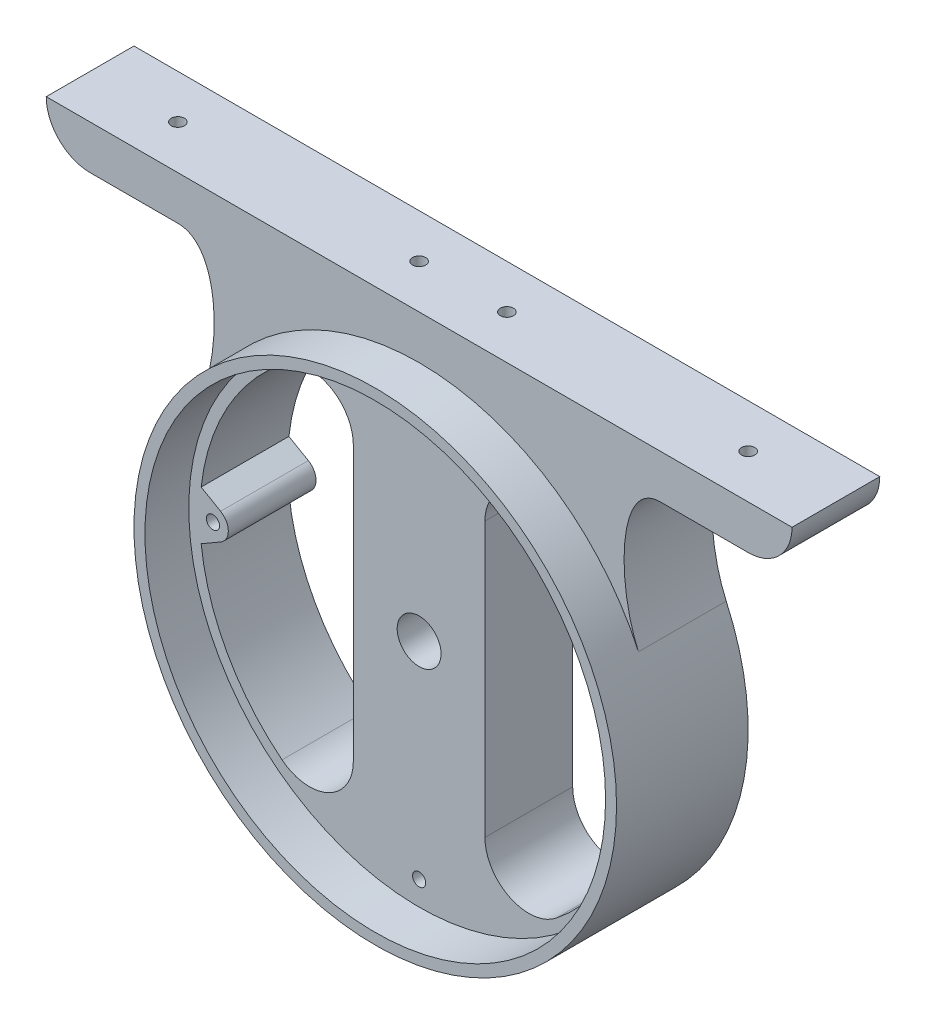
SolidWorks part; units mm, degrees
ref_plane "前视基准面" through (0, 0, 0) normal (0, 0, 1) x (1, 0, 0)
ref_plane "上视基准面" through (0, 0, 0) normal (0, 1, 0) x (1, 0, 0)
ref_plane "右视基准面" through (0, 0, 0) normal (1, 0, 0) x (0, 0, -1)
sketch "草图2" plane through (0, 0, 0) normal (0, 0, 1) x (1, 0, 0)
  line L0 (0, 55) -> (37.8067, 55) construction
  line L1 (-55, 0) -> (-55, 32.093) construction
  line L2 (-45, 109.1596) -> (-45, 87.8343) construction
  line L3 (-55, 55) -> (-85, 55) construction
  line L4 (-85, 55) -> (-85, 65) construction
  line L5 (-75, 55) -> (-55, 55)
  line L6 (0, 104.3034) -> (0, 77.4884) construction
  line L7 (85, 55) -> (85, 65) construction
  line L8 (55, 55) -> (85, 55) construction
  line L9 (75, 55) -> (55, 55)
  line L10 (-85, 65) -> (85, 65)
  line L11 (-15, 47.697) -> (-15, -47.697)
  line L12 (15, 47.697) -> (15, -47.697)
  line L13 (-50, 22.9129) -> (-45, 33.8238) construction
  line L14 (-45, 33.8238) -> (-45, 55) construction
  line L15 (-45, 55) -> (-55, 55) construction
  line L16 (50, 22.9129) -> (45, 33.8238) construction
  line L17 (45, 33.8238) -> (45, 55) construction
  line L18 (45, 55) -> (55, 55) construction
  arc A0 (-15, 47.697) -> (-15, -47.697) centre (0, 0) ccw
  circle A1 centre (0, 0) radius 55 construction
  arc A2 (-85, 65) -> (-75, 55) centre (-75, 65) ccw
  arc A3 (85, 65) -> (75, 55) centre (75, 65) cw
  arc A4 (-50, 22.9129) -> (50, 22.9129) centre (0, 0) ccw
  arc A5 (15, -47.697) -> (15, 47.697) centre (0, 0) ccw
  circle A6 centre (0, 0) radius 5
  spline S0 degree 3 poles (-50, 22.9129) (-45, 33.8238) (-45, 55) (-55, 55) knots 0 0 0 0 1 1 1 1
  spline S1 degree 3 poles (50, 22.9129) (45, 33.8238) (45, 55) (55, 55) knots 0 0 0 0 1 1 1 1
  point P33 (49.3321, 24.507)
  dimension "D1" = 110
  dimension "D2" = 100
  dimension "D3" = 10
  dimension "D5" = 10
  dimension "D6" = 15
  dimension "D7" = 10
  dimension "D4" = 30
  dimension "D8" = 5
extrude "凸台-拉伸1" add sketch "草图2" along normal blind 20
sketch "草图3" plane through (0, 65, 0) normal (0, 1, 0) x (1, 0, 0)
  line L0 (0, 0) -> (0, -20) construction
  line L2 (-85, -10) -> (-55.1419, -10) construction
  line L4 (-85, -20) -> (-85, 0) construction
  circle A0 centre (-65, -10) radius 1.5
  circle A1 centre (-10, -10) radius 1.5
  circle A2 centre (10, -10) radius 1.5
  circle A3 centre (65, -10) radius 1.5
  point P5 (-85, -10)
  dimension "D1" = 3
  dimension "D2" = 10
  dimension "D3" = 55
extrude "切除-拉伸1" cut sketch "草图3" against normal through all
fillet "圆角1" radius 10 4 edges at (-15, 47.697, 10) (15, 47.697, 10) (15, -47.697, 10) (-15, -47.697, 10)
sketch "草图4" plane through (0, 0, 0) normal (0, 0, 1) x (1, 0, 0)
  line L0 (0, 0) -> (-31.4748, 0) construction
  line L1 (-49.6863, 5.5924) -> (-45.25, 3.0311)
  line L2 (-49.6863, -5.5924) -> (-45.25, -3.0311)
  line L3 (0, 0) -> (0, 13.1846) construction
  line L4 (49.6863, -5.5924) -> (45.25, -3.0311)
  line L5 (49.6863, 5.5924) -> (45.25, 3.0311)
  circle A0 centre (-47, 0) radius 1.5
  arc A1 (-31.25, 39.0312) -> (-31.25, -39.0312) centre (0, 0) ccw construction
  arc A2 (-45.25, 3.0311) -> (-45.25, -3.0311) centre (-47, 0) cw
  arc A3 (-49.6863, 5.5924) -> (-49.6863, -5.5924) centre (0, 0) ccw
  arc A4 (49.6863, 5.5924) -> (49.6863, -5.5924) centre (0, 0) cw
  arc A5 (45.25, 3.0311) -> (45.25, -3.0311) centre (47, 0) ccw
  circle A6 centre (47, 0) radius 1.5
  dimension "D1" = 30
  dimension "D2" = 2
  dimension "D3" = 3
  dimension "D4" = 47
extrude "凸台-拉伸2" add sketch "草图4" along normal through all
sketch "草图5" plane through (0, 0, 0) normal (0, 0, 1) x (1, 0, 0)
  line L0 (0, 16.9938) -> (0, 50.6639) construction
  line L1 (0, 0) -> (16.2571, 0) construction
  circle A0 centre (0, 47) radius 1.5
  circle A2 centre (0, -47) radius 1.5
  dimension "D1" = 3
  dimension "D2" = 47
extrude "切除-拉伸3" cut sketch "草图5" along normal through all
sketch "草图6" plane through (0, 0, 0) normal (0, 1, 0) x (1, 0, 0)
  line L0 (85, 0) -> (-85, 0) construction
  line L1 (-8.4123, -7.25) -> (-11.5877, -7.25)
  line L2 (-11.5877, -7.25) -> (-13.1754, -10)
  line L3 (-13.1754, -10) -> (-11.5877, -12.75)
  line L4 (-11.5877, -12.75) -> (-8.4123, -12.75)
  line L5 (-8.4123, -12.75) -> (-6.8246, -10)
  line L6 (-6.8246, -10) -> (-8.4123, -7.25)
  line L7 (0, 0) -> (0, -20) construction
  line L8 (85, -20) -> (-85, -20) construction
  line L9 (6.8246, -10) -> (8.4123, -7.25)
  line L10 (8.4123, -12.75) -> (6.8246, -10)
  line L11 (11.5877, -12.75) -> (8.4123, -12.75)
  line L12 (13.1754, -10) -> (11.5877, -12.75)
  line L13 (11.5877, -7.25) -> (13.1754, -10)
  line L14 (8.4123, -7.25) -> (11.5877, -7.25)
  circle A0 centre (-10, -10) radius 2.75 construction
  circle A1 centre (10, -10) radius 2.75 construction
  point P11 (-12.3816, -11.375)
  dimension "D1" = 5.5
extrude "切除-拉伸4" cut sketch "草图6" against normal through all from offset 52 offset against normal yes
sketch "草图7" plane through (0, 55, 0) normal (0, -1, 0) x (1, 0, 0)
  line L0 (-75, 20) -> (-55, 20) construction
  line L1 (-63.4123, 12.75) -> (-66.5877, 12.75)
  line L2 (-66.5877, 12.75) -> (-68.1754, 10)
  line L3 (-68.1754, 10) -> (-66.5877, 7.25)
  line L4 (-66.5877, 7.25) -> (-63.4123, 7.25)
  line L5 (-63.4123, 7.25) -> (-61.8246, 10)
  line L6 (-61.8246, 10) -> (-63.4123, 12.75)
  line L7 (0, 0) -> (0, 40.9385) construction
  line L9 (61.8246, 10) -> (63.4123, 12.75)
  line L10 (63.4123, 7.25) -> (61.8246, 10)
  line L11 (66.5877, 7.25) -> (63.4123, 7.25)
  line L12 (68.1754, 10) -> (66.5877, 7.25)
  line L13 (66.5877, 12.75) -> (68.1754, 10)
  line L14 (63.4123, 12.75) -> (66.5877, 12.75)
  circle A0 centre (-65, 10) radius 2.75 construction
  circle A1 centre (65, 10) radius 2.75 construction
  dimension "D1" = 5.5
extrude "切除-拉伸5" cut sketch "草图7" against normal blind 2
sketch "草图9" plane through (0, 0, 20) normal (0, 0, 1) x (1, 0, 0)
  circle A0 centre (0, 0) radius 50
  circle A1 centre (0, 0) radius 55
extrude "凸台-拉伸3" add sketch "草图9" along normal blind 10
sketch "草图10" plane through (0, 0, 30) normal (0, 0, 1) x (1, 0, 0)
  circle A0 centre (0, 0) radius 50
  circle A1 centre (0, 0) radius 52.5
  circle A2 centre (0, 0) radius 50 construction
  dimension "D1" = 2.5
extrude "切除-拉伸6" cut sketch "草图10" against normal blind 10
